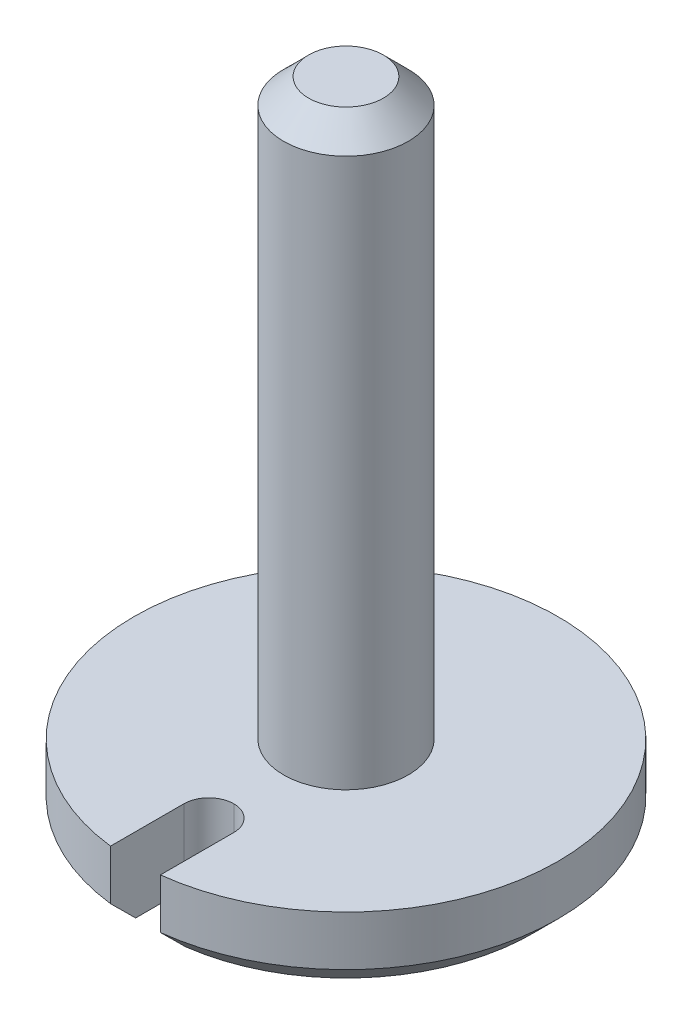
SolidWorks part; units mm, degrees
material "Gray Cast Iron"
ref_plane "Front" through (0, 0, 0) normal (0, 0, 1) x (1, 0, 0)
ref_plane "Top" through (0, 0, 0) normal (0, 1, 0) x (1, 0, 0)
ref_plane "Right" through (0, 0, 0) normal (1, 0, 0) x (0, 0, -1)
sketch "Sketch1" plane through (0, 0, 0) normal (0, 1, 0) x (1, 0, 0)
  circle A0 centre (0, 0) radius 2.5
extrude "Boss-Extrude1" add sketch "Sketch1" along normal blind 23
chamfer "Chamfer1" distance 1 angle 45 1 edges at (0, 23, 2.5)
sketch "Sketch2" plane through (0, 0, 0) normal (0, -1, 0) x (1, 0, 0)
  circle A0 centre (0, 0) radius 8.5
extrude "Boss-Extrude2" add sketch "Sketch2" along normal blind 3
sketch "Sketch3" plane through (0, -3, 0) normal (0, -1, 0) x (1, 0, 0)
  line L0 (0, 8.8651) -> (0, 0) construction
  line L2 (-1, 12.5) -> (1, 12.5)
  line L3 (-1, 12.5) -> (-1, 4.5)
  line L4 (-1, 4.5) -> (1, 4.5)
  line L5 (1, 12.5) -> (1, 4.5)
  line L6 (-1, 12.5) -> (1, 4.5) construction
  line L7 (-1, 4.5) -> (1, 12.5) construction
  circle A0 centre (0, 0) radius 8.5 construction
  point P3 (0, 8.5)
  dimension "D1" = 8
  dimension "D2" = 2
extrude "Cut-Extrude1" cut sketch "Sketch3" against normal blind 3
fillet "Fillet1" radius 1 2 edges at (-1, -1.5, 4.5) (1, -1.5, 4.5)
chamfer "Chamfer2" distance 1 angle 45 1 edges at (0, -3, -8.5)
